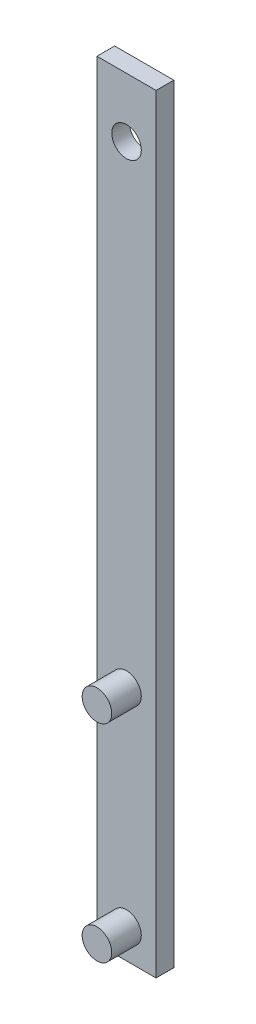
SolidWorks part; units mm, degrees
ref_plane "Plano frontal" through (0, 0, 0) normal (0, 0, 1) x (1, 0, 0)
ref_plane "Plano superior" through (0, 0, 0) normal (0, 1, 0) x (1, 0, 0)
ref_plane "Plano direito" through (0, 0, 0) normal (1, 0, 0) x (0, 0, -1)
sketch "Esboço1" plane through (0, 0, 0) normal (0, 0, 1) x (1, 0, 0)
  line L1 (-5, -65) -> (5, -65)
  line L2 (-5, -65) -> (-5, 65)
  line L3 (-5, 65) -> (5, 65)
  line L4 (5, -65) -> (5, 65)
  line L5 (-5, -65) -> (5, 65) construction
  line L6 (-5, 65) -> (5, -65) construction
  circle A0 centre (0, 55) radius 2.5
  circle A1 centre (0, -60) radius 2.5
  circle A2 centre (0, -25) radius 2.5
  point P0 (0, 0)
  point P12 (0, 0)
  point P13 (0, 0)
  dimension "D3" = 5
  dimension "D4" = 5
  dimension "D7" = 5
  dimension "D1" = 130
  dimension "D2" = 10
  dimension "D5" = 5
  dimension "D6" = 5
  dimension "D8" = 35
  dimension "D9" = 5
  dimension "D10" = 10
  dimension "D11" = 5
extrude "Ressalto-extrusão1" add sketch "Esboço1" along normal blind 3 contours L2 L1 L4 L3 | A2 | A1 | A0
extrude "Ressalto-extrusão7" add sketch "Esboço1<11>" along normal blind 8 contours A2 | A1 region at (0, -60, 0) region at (0, -25, 0)
sketch "Esboço1<11>" plane through (0, 0, 0) normal (0, 0, 1) x (1, 0, 0) same geometry as "Esboço1"
